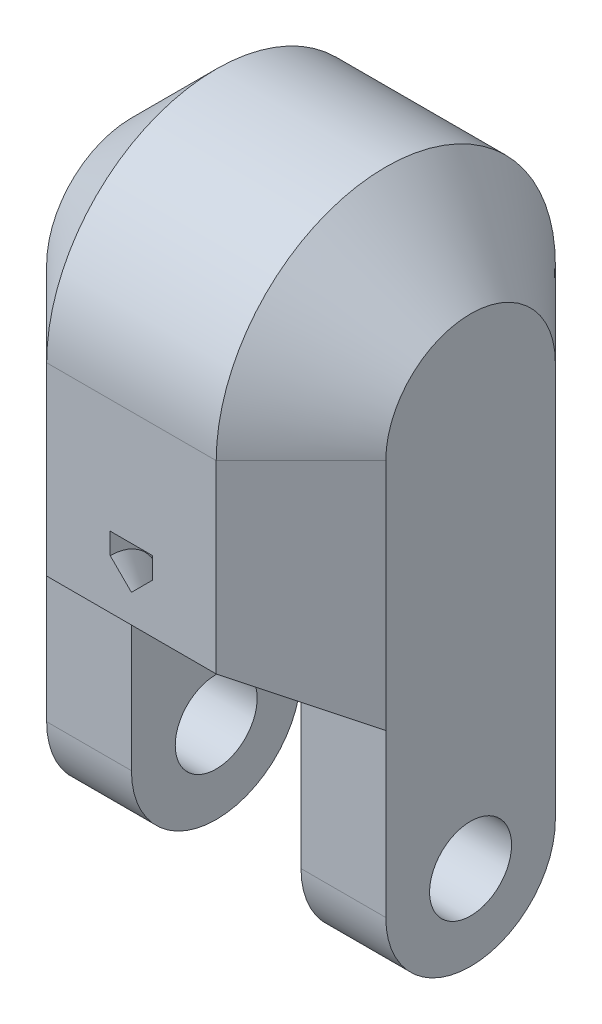
SolidWorks part; units mm, degrees
ref_plane "Front Plane" through (0, 0, 0) normal (0, 0, 1) x (1, 0, 0)
ref_plane "Top Plane" through (0, 0, 0) normal (0, 1, 0) x (1, 0, 0)
ref_plane "Right Plane" through (0, 0, 0) normal (1, 0, 0) x (0, 0, -1)
sketch "Sketch2" plane through (0, 0, 0) normal (0, 1, 0) x (1, 0, 0)
  line L0 (-3, 6) -> (3, 6)
  line L1 (3, 6) -> (6, 3)
  line L2 (6, 3) -> (6, -3)
  line L3 (6, -3) -> (3, -6)
  line L4 (3, -6) -> (-3, -6)
  line L5 (-3, -6) -> (-6, -3)
  line L6 (-6, -3) -> (-6, 3)
  line L7 (-6, 3) -> (-3, 6)
  point P2 (0, -6)
  point P9 (0, 6)
  point P12 (-6, 0)
  point P13 (6, 0)
  dimension "D1" = 12
  dimension "D2" = 12
  dimension "D3" = 6
  dimension "D4" = 6
  dimension "D5" = 6
extrude "Boss-Extrude1" add sketch "Sketch2" along normal mid plane 10 contours L7 L0 L1 L2 L3 L4 L5 L6
sketch "Sketch22" plane through (0, 0, 0) normal (1, 0, 0) x (0, 0, -1)
  line L0 (0, -5) -> (-6, -5)
  line L1 (3, -5) -> (-3, -5) construction
  line L2 (-6, -5) -> (-6, -1.5359)
  line L3 (-6, 5) -> (-6, -5) construction
  line L4 (-6, -1.5359) -> (0, -5)
  dimension "D1" = 30
extrude "Cut-Extrude8" cut sketch "Sketch22" against normal through all both and the other way through all
sketch "Sketch23" plane through (0, 5, 0) normal (0, 1, 0) x (1, 0, 0)
  line L0 (-6, 0) -> (-6, 3)
  line L1 (-6, -3) -> (-6, 3) construction
  line L2 (-6, 3) -> (-3, 6)
  line L3 (-3, 6) -> (3, 6)
  line L4 (3, 6) -> (6, 3)
  line L5 (6, 3) -> (6, 0)
  line L6 (6, 3) -> (6, -3) construction
  line L7 (6, 0) -> (-6, 0)
revolve "Revolve1" add sketch "Sketch23" angle 180 about L7 reverse direction yes
sketch "Sketch24" plane through (0, -5, 0) normal (0, -1, 0) x (1, 0, 0)
  line L1 (-6, -3) -> (-3, -3)
  line L2 (-6, -3) -> (-6, 3)
  line L3 (-6, 3) -> (-3, 3)
  line L4 (-3, -3) -> (-3, 3)
  point P5 (0, 0)
  dimension "D1" = 3
extrude "Boss-Extrude2" add sketch "Sketch24" along normal mid plane 8
sketch "Sketch25" plane through (0, -9, 0) normal (0, -1, 0) x (1, 0, 0)
  line L0 (-6, 3) -> (-6, -3) construction
  line L1 (-6, 0) -> (-3, 0)
  line L2 (-6, 0) -> (-6, 3)
  line L3 (-6, 3) -> (-3, 3)
  line L4 (-3, 0) -> (-3, 3)
revolve "Revolve2" add sketch "Sketch25" angle 180 about L1
sketch "Sketch26" plane through (-6, 0, 0) normal (-1, 0, 0) x (0, 0, 1)
  line L0 (-3, -9) -> (3, -9) construction
  circle A0 centre (0, -9) radius 1.45
  dimension "D1" = 2.9
extrude "Cut-Extrude9" cut sketch "Sketch26" against normal through all both and the other way through all
mirror "Mirror1" about plane through (0, 0, 0) normal (1, 0, 0) of "Revolve2", "Cut-Extrude9", "Boss-Extrude2"
sketch "Sketch30" plane through (0, -3.75, 2.1651) normal (0, -0.866, 0.5) x (1, 0, 0)
  line L0 (0, 3.4282) -> (-0.75, 2.6782)
  line L1 (-0.75, 2.6782) -> (-0.75, 1.9282)
  line L2 (-0.75, 1.9282) -> (0.75, 1.9282)
  line L3 (0.75, 1.9282) -> (0.75, 2.6782)
  line L4 (0.75, 2.6782) -> (0, 3.4282)
  line L5 (-3, 4.4282) -> (3, 4.4282) construction
  point P2 (0, 0)
  point P6 (0, 0)
  point P7 (0, 0)
  point P10 (0, 4.4282)
  dimension "D1" = 135
  dimension "D2" = 0.75
  dimension "D3" = 1.5
  dimension "D4" = 1
revolve "Cut-Revolve1" cut sketch "Sketch30" angle 360 about axis through (-6, -1.5359, 6) along (1, 0, 0)
sketch "Sketch34" plane through (0, -5, 0) normal (0, -1, 0) x (1, 0, 0)
  line L0 (-6, -3) -> (-3, -3)
  line L1 (-3, -3) -> (3, -3)
  line L2 (3, -3) -> (6, -3)
  line L3 (6, -3) -> (3, -6)
  line L4 (3, -6) -> (-3, -6)
  line L5 (-3, -6) -> (-6, -3)
extrude "Boss-Extrude4" add sketch "Sketch34" along normal blind 3.75
sketch "Sketch35" plane through (0, -8.75, 0) normal (0, -1, 0) x (1, 0, 0)
  line L0 (0, -3.5) -> (-0.75, -4.25)
  line L1 (-0.75, -4.25) -> (-0.75, -5)
  line L2 (-0.75, -5) -> (0.75, -5)
  line L3 (0.75, -5) -> (0.75, -4.25)
  line L4 (0.75, -4.25) -> (0, -3.5)
  line L5 (-3, -6) -> (3, -6) construction
  point P7 (0, 0)
  dimension "D1" = 1.5
  dimension "D2" = 1.5
  dimension "D3" = 1
  dimension "D4" = 135
revolve "Cut-Revolve3" cut sketch "Sketch35" angle 360 about axis through (3, -8.75, -6) along (1, 0, 0)
